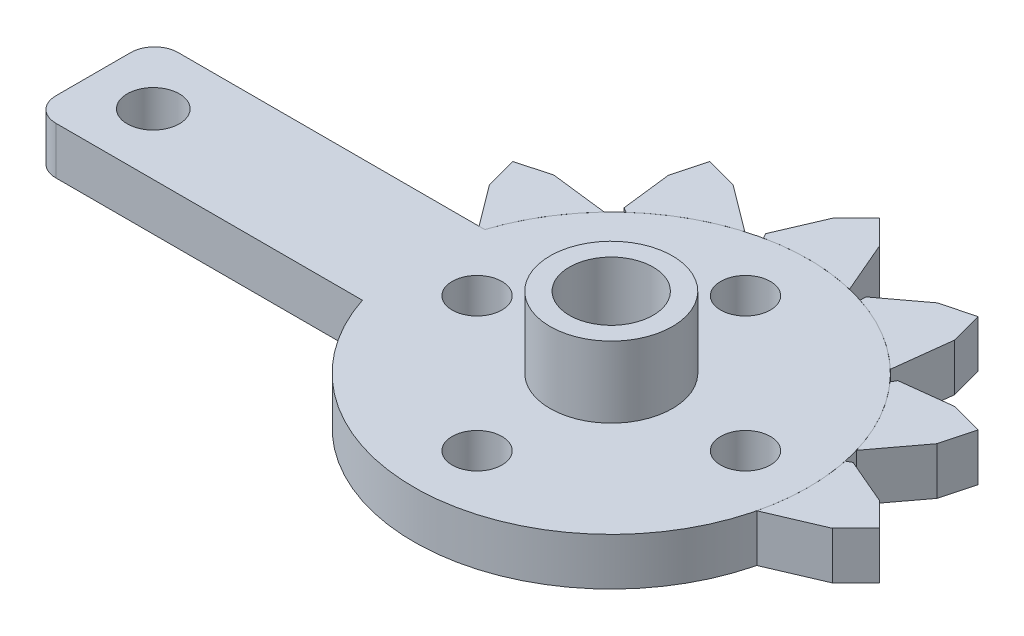
SolidWorks part; units mm, degrees
note: The reader was unsure of these and kept them because the rebuilt part matched: shared geometry of "Sketch1<3>", "Sketch1<5>".
ref_plane "Front Plane" through (0, 0, 0) normal (0, 0, 1) x (1, 0, 0)
ref_plane "Top Plane" through (0, 0, 0) normal (0, 1, 0) x (1, 0, 0)
ref_plane "Right Plane" through (0, 0, 0) normal (1, 0, 0) x (0, 0, -1)
sketch "Sketch1" plane through (0, 0, 0) normal (0, 1, 0) x (1, 0, 0)
  line L0 (-3.875, 0) -> (-3.875, 12.8)
  line L1 (-3.875, 12.8) -> (3.875, 12.8)
  line L2 (3.875, 12.8) -> (3.875, 0)
  line L3 (0, 0) -> (0, 8.5)
  line L4 (0, 3.875) -> (12.8, 3.875)
  line L5 (12.8, 3.875) -> (12.8, -3.875)
  line L6 (12.8, -3.875) -> (0, -3.875)
  line L7 (3.875, 0) -> (3.875, -12.8)
  line L8 (3.875, -12.8) -> (-3.875, -12.8)
  line L9 (-3.875, -12.8) -> (-3.875, 0)
  line L10 (0, -3.875) -> (-12.8, -3.875)
  line L11 (-12.8, -3.875) -> (-12.8, 3.875)
  line L12 (-12.8, 3.875) -> (0, 3.875)
  line L13 (-12.8, -3.875) -> (-32.8, -3.875)
  line L14 (-32.8, -3.875) -> (-32.8, 3.875)
  line L15 (-32.8, 3.875) -> (-12.8, 3.875)
  line L16 (0, 0) -> (-29, 0)
  circle A0 centre (0, 0) radius 2.65
  circle A1 centre (0, 0) radius 5.25
  circle A2 centre (0, 0) radius 3.875
  circle A3 centre (0, 8.5) radius 1.575
  circle A4 centre (8.5, 0) radius 1.575
  circle A5 centre (0, -8.5) radius 1.575
  circle A6 centre (-8.5, 0) radius 1.575
  circle A7 centre (0, 0) radius 12.5
  circle A8 centre (-29, 0) radius 1.65
  circle A9 centre (0, 0) radius 1.125
  circle A10 centre (0, 0) radius 3
  point P26 (0, 0)
  point P29 (0, 0)
  dimension "D1" = 5.3
  dimension "D2" = 10.5
  dimension "D3" = 7.75
  dimension "D5" = 3.15
  dimension "D9" = 25
  dimension "D13" = 3.3
  dimension "D14" = 2.25
  dimension "D15" = 6
  dimension "D4" = 8.5
  dimension "D6" = 7.75
  dimension "D10" = 12.8
  dimension "D11" = 20
  dimension "D12" = 29
  dimension "D7" = 4
  dimension "D8" = 4
extrude "Boss-Extrude1" add sketch "Sketch1" along normal blind 3
extrude "Boss-Extrude2" add sketch "Sketch1<3>" along normal blind 7.5
sketch "Sketch1<3>" plane through (0, 0, 0) normal (0, 1, 0) x (1, 0, 0) same geometry as "Sketch1"
sketch "Sketch5" plane through (0, 3, 0) normal (0, 1, 0) x (1, 0, 0)
  line L0 (0, 0) -> (-10.8253, 6.25)
  line L4 (-14.174, 6.4513) -> (-14.7224, 8.5)
  line L5 (-12.674, 9.0494) -> (-14.7224, 8.5)
  line L32 (-11.8923, 3.4019) -> (-13.6244, 4.4019)
  line L33 (-8.8923, 8.5981) -> (-10.6244, 9.5981)
  line L34 (-8.8923, 8.5981) -> (-14.7224, 8.5)
  line L35 (-14.7224, 8.5) -> (-11.8923, 3.4019)
  line L44 (-14.7224, 8.5) -> (-10.8253, 6.25)
  line L45 (-14.174, 6.4513) -> (-12.674, 9.0494)
  line L46 (-11.8923, 3.4019) -> (-14.174, 6.4513)
  line L47 (-8.8923, 8.5981) -> (-12.674, 9.0494)
  arc A11 (-13.6244, 4.4019) -> (-10.6244, 9.5981) centre (-12.1244, 7) cw
  arc A13 (-11.8842, -3.875) -> (-11.8842, 3.875) centre (0, 0) ccw construction
  point P73 (-13.424, 7.7504)
  arc M13 (-11.8842, -3.875) -> (-11.8842, 3.875) centre (0, 0) ccw
  line M14 (-11.8842, 3.875) -> (-32.8, 3.875)
  dimension "D5" = 3
extrude "Boss-Extrude3" add sketch "Sketch5" against normal blind 3 separate body contours L46 L35 L45 M14 | L4 L45 L35 | L35 L45 L44 | L44 L45 L34 | L34 L45 L5 | L47 L45 L34 M13 | L45 L44 L34 M13 | L45 L35 L44 M14 M13
fillet "Fillet2" radius 1.5 2 edges at (-32.8, 1.5, 3.875) (-32.8, 1.5, -3.875)
pattern_circular "CirPattern2" count 6 every 30 about axis through (0, 0, 0) along (0, 1, 0) of bodies 104
extrude "Boss-Extrude4" add sketch "Sketch1<5>" along normal blind 0.75 from offset 3 contours A9 L16 A0 L3 | A9 L3 A0 L16
sketch "Sketch1<5>" plane through (0, 0, 0) normal (0, 1, 0) x (1, 0, 0) same geometry as "Sketch1"
